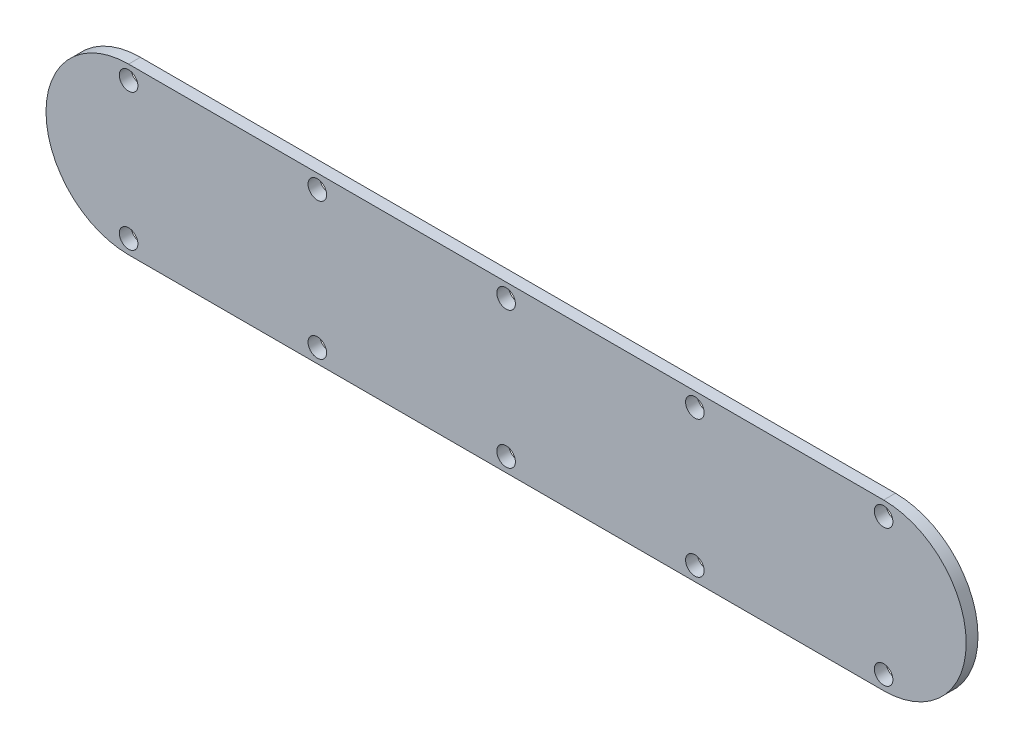
SolidWorks part; units mm, degrees
material "6061 Alloy"
ref_plane "Front" through (0, 0, 0) normal (0, 0, 1) x (1, 0, 0)
ref_plane "Top" through (0, 0, 0) normal (0, 1, 0) x (1, 0, 0)
ref_plane "Right" through (0, 0, 0) normal (1, 0, 0) x (0, 0, -1)
sketch "Sketch1" plane through (0, 0, 0) normal (0, 0, 1) x (1, 0, 0)
  line L1 (123.825, 22.225) -> (-123.825, 22.225)
  line L2 (123.825, 22.225) -> (123.825, -22.225)
  line L3 (123.825, -22.225) -> (-123.825, -22.225)
  line L4 (-123.825, 22.225) -> (-123.825, -22.225)
  line L5 (123.825, 22.225) -> (-123.825, -22.225) construction
  line L6 (123.825, -22.225) -> (-123.825, 22.225) construction
  point P0 (0, 0)
  dimension "D1" = 247.65
  dimension "D2" = 44.45
extrude "Boss-Extrude1" add sketch "Sketch1" along normal blind 3.175
sketch "Sketch2" plane through (0, 0, 3.175) normal (0, 0, 1) x (1, 0, 0)
  line L0 (101.6, 0) -> (-101.6, 0) construction
  line L1 (101.6, -14.351) -> (-101.6, -14.351)
  line L2 (101.6, 14.351) -> (-101.6, 14.351)
  line L3 (101.6, -22.225) -> (-101.6, -22.225)
  line L4 (101.6, 22.225) -> (-101.6, 22.225)
  arc A0 (101.6, -14.351) -> (101.6, 14.351) centre (101.6, 0) ccw
  arc A1 (-101.6, 14.351) -> (-101.6, -14.351) centre (-101.6, 0) ccw
  arc A2 (-101.6, 22.225) -> (-101.6, -22.225) centre (-101.6, 0) ccw
  arc A3 (101.6, -22.225) -> (101.6, 22.225) centre (101.6, 0) ccw
  point P2 (0, 0)
  line M9 (-123.825, 22.225) -> (-123.825, -22.225)
  line M10 (-123.825, -22.225) -> (123.825, -22.225)
  line M11 (123.825, -22.225) -> (123.825, 22.225)
  line M12 (123.825, 22.225) -> (-123.825, 22.225)
  dimension "D1" = 203.2
  dimension "D2" = 28.702
  dimension "D3" = 7.874
extrude "Cut-Extrude1" cut sketch "Sketch2" against normal through all contours A2 M12 M9 | A2 M9 M10 | A3 M10 M11 | A3 M11 M12 region at (118.8606, -17.2606, 3.175) region at (-118.8606, -17.2606, 3.175) region at (118.8606, 17.2606, 3.175) region at (-118.8606, 17.2606, 3.175)
sketch "Sketch3" plane through (0, 0, 3.175) normal (0, 0, 1) x (1, 0, 0)
  line L2 (101.6, 18.415) -> (-101.6, 18.415)
  line L3 (101.6, 18.415) -> (-101.6, 18.415) construction
  line L4 (-101.6, 18.415) -> (0, 18.415) construction
  line L5 (-101.6, -18.415) -> (101.6, -18.415)
  line L6 (-101.6, -18.415) -> (101.6, -18.415) construction
  line L7 (0, 18.415) -> (101.6, 18.415) construction
  line L8 (-101.6, -18.415) -> (0, -18.415) construction
  line L9 (0, -18.415) -> (101.6, -18.415) construction
  point P0 (0, 18.415)
  point P1 (-101.6, 18.415)
  point P6 (0, -18.415)
  point P7 (101.6, 18.415)
  point P8 (101.6, -18.415)
  point P9 (-50.8, 18.415)
  point P10 (-101.6, -18.415)
  point P13 (50.8, 18.415)
  point P14 (-50.8, -18.415)
  point P15 (50.8, -18.415)
  dimension "D1" = 3.81
  dimension "D2" = 3.81
hole_wizard "#10 (0.1935) Diameter Hole1" positions "Sketch6" profile "Sketch7" hole size "#10" standard "ANSI Inch" end condition through all
sketch "Sketch6" plane through (0, 0, 3.175) normal (0, 0, 1) x (1, 0, 0)
  point P0 (-101.6, 18.415)
  point P3 (-50.8, 18.415)
  point P6 (0, 18.415)
  point P9 (50.8, 18.415)
  point P12 (101.6, 18.415)
  point P15 (101.6, -18.415)
  point P18 (50.8, -18.415)
  point P21 (0, -18.415)
  point P24 (-50.8, -18.415)
  point P27 (-101.6, -18.415)
sketch "Sketch7" plane through (-101.6, 18.415, 3.175) normal (1, 0, 0) x (0, -1, 0)
  line L0 (0, 0) -> (0, 3.175)
  line L1 (0, 3.175) -> (2.5, 3.175)
  line L2 (2.5, 3.175) -> (2.5, 0)
  line L5 (2.5, 0) -> (0, 0)
  line L11 (0, -6.35) -> (0, 107.95) construction
  dimension "Thru Hole Dia." = 5
  dimension "Thru Hole Depth" = 3.175
